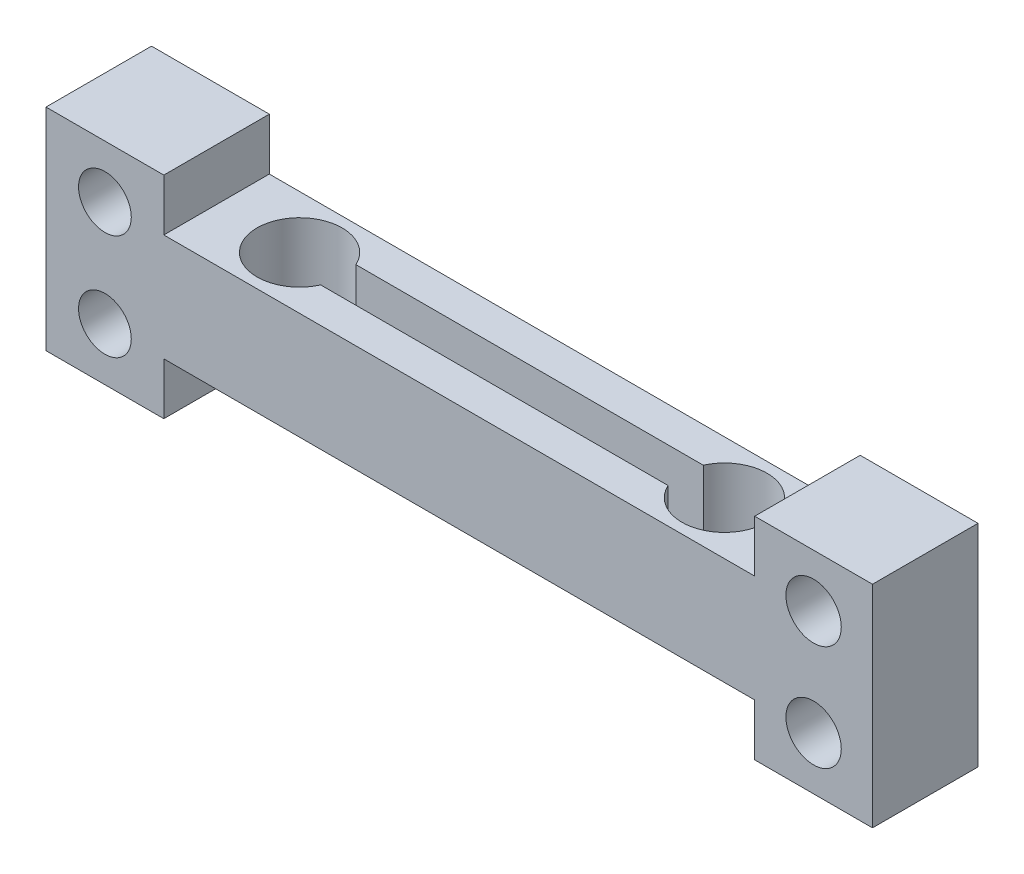
SolidWorks part; units mm, degrees
ref_plane "Front Plane" through (0, 0, 0) normal (0, 0, 1) x (1, 0, 0)
ref_plane "Top Plane" through (0, 0, 0) normal (0, 1, 0) x (1, 0, 0)
ref_plane "Right Plane" through (0, 0, 0) normal (1, 0, 0) x (0, 0, -1)
sketch "Sketch1" plane through (0, 0, 0) normal (0, 0, 1) x (1, 0, 0)
  line L0 (40.3, 3) -> (40.3, -3) construction
  line L1 (-3.35, 6) -> (3.35, 6)
  line L2 (-3.35, 6) -> (-3.35, -6)
  line L3 (-3.35, -6) -> (3.35, -6)
  line L4 (3.35, 6) -> (3.35, 3.05)
  line L5 (-3.35, 6) -> (3.35, -6) construction
  line L6 (-3.35, -6) -> (3.35, 6) construction
  line L7 (43.65, -6) -> (36.95, -6)
  line L8 (43.65, -6) -> (43.65, 6)
  line L9 (43.65, 6) -> (36.95, 6)
  line L10 (36.95, -6) -> (36.95, -3.05)
  line L11 (43.65, -6) -> (36.95, 6) construction
  line L12 (43.65, 6) -> (36.95, -6) construction
  line L13 (0, 3) -> (0, -3) construction
  line L14 (3.35, -3.05) -> (3.35, -6)
  line L15 (3.35, 3.05) -> (36.95, 3.05)
  line L17 (3.35, -3.05) -> (36.95, -3.05)
  line L19 (36.95, 3.05) -> (36.95, 6)
  line L20 (20.15, 3.05) -> (20.15, -3.05) construction
  circle A0 centre (40.3, 3) radius 1.575
  circle A1 centre (40.3, -3) radius 1.575
  circle A2 centre (0, 3) radius 1.5
  circle A3 centre (0, -3) radius 1.5
  point P0 (0, 0)
  point P6 (40.3, 0)
  point P15 (40.3, 0)
  point P17 (41.875, 3)
  point P20 (0, 0)
  point P24 (-1.5, 3)
  point P29 (20.15, 0)
  dimension "D5" = 3.15
  dimension "D6" = 6
  dimension "D7" = 3
  dimension "D8" = 6
  dimension "D1" = 12
  dimension "D2" = 6.7
  dimension "D3" = 47
  dimension "D4" = 6.7
  dimension "D9" = 6.1
extrude "Boss-Extrude1" add sketch "Sketch1" along normal mid plane 6
sketch "Sketch4" plane through (0, 0, 3) normal (0, 1, 0) x (1, 0, 0)
  line L0 (10.2737, 4) -> (30.0263, 4)
  line L1 (10.2737, 2) -> (30.0263, 2)
  line L2 (8.07, 3) -> (32.23, 3) construction
  line L3 (36.95, 0) -> (3.35, 0) construction
  arc A0 (10.2737, 4) -> (10.2737, 2) centre (8.07, 3) ccw
  arc A1 (30.0263, 2) -> (30.0263, 4) centre (32.23, 3) ccw
  point P8 (5.65, 3)
  point P9 (20.15, 3)
  point P10 (34.65, 3)
  point P11 (20.15, 0)
  dimension "D1" = 4.84
  dimension "D2" = 1
  dimension "D3" = 2
  dimension "D4" = 29
extrude "Cut-Extrude2" cut sketch "Sketch4" against normal through all both and the other way through all
ref_axis "Axis1" through (0, 3, 3) along (0, 0, -1)
